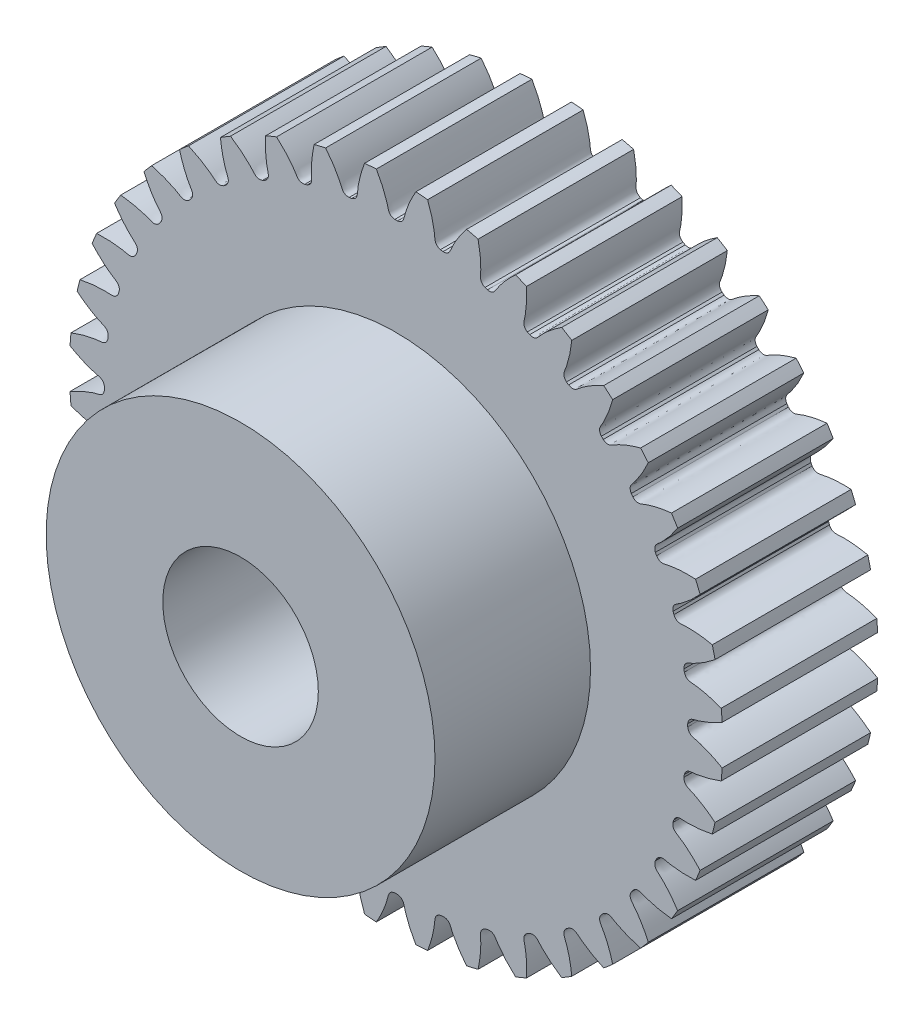
SolidWorks part; units mm, degrees
material "合金钢 (SS)"
ref_plane "前视基准面" through (0, 0, 0) normal (0, 0, 1) x (1, 0, 0)
ref_plane "上视基准面" through (0, 0, 0) normal (0, 1, 0) x (1, 0, 0)
ref_plane "右视基准面" through (0, 0, 0) normal (1, 0, 0) x (0, 0, -1)
other "Configuration Table"
sketch "草图1" plane through (0, 0, 0) normal (0, 0, 1) x (1, 0, 0)
  circle A0 centre (0, 0) radius 21
extrude "凸台-拉伸1" add sketch "草图1" along normal blind 10
ref_axis "基准轴1" through (0, 0, -1.5) along (0, 0, 1)
sketch "草图2" plane through (0, 0, 0) normal (0, 0, 1) x (1, 0, 0)
  line L0 (0, 0) -> (0, 21) construction
  circle A0 centre (0, 0) radius 21 construction
  arc A1 (0.0846, 18.7498) -> (-0.0846, 18.7498) centre (0, 0) ccw
  arc A2 (3.6741, 23.878) -> (-3.6741, 23.878) centre (0, 0) ccw
  spline S0 degree 3 poles (0.0846, 18.7498) (0.4557, 18.804) (0.4895, 19.0705) (0.567, 19.3562) (0.5939, 19.4493) (0.625, 19.5489) (0.6605, 19.6551) (0.7006, 19.7676) (0.7456, 19.8863) (0.7958, 20.011) (0.8514, 20.1417) (0.9127, 20.2781) (0.9799, 20.42) (1.0533, 20.5672) (1.1331, 20.7197) (1.2196, 20.8771) (1.3129, 21.0392) (1.4134, 21.2059) (1.5211, 21.3769) (1.6364, 21.552) (1.7595, 21.731) (1.8904, 21.9136) (2.0295, 22.0995) (2.1769, 22.2885) (2.3328, 22.4804) (2.4974, 22.6749) (2.6708, 22.8717) (2.8532, 23.0705) (3.0447, 23.2711) (3.3159, 23.5441) (3.5282, 23.7451) (3.6741, 23.878) knots 0 0 0 0 0.110657 0.124739 0.140005 0.156457 0.174093 0.192913 0.212918 0.234108 0.256483 0.280042 0.304786 0.330714 0.357827 0.386125 0.415607 0.446274 0.478126 0.511162 0.545383 0.580789 0.617379 0.655154 0.694113 0.734257 0.775586 0.8181 0.861798 0.906681 1 1 1 1
  spline S1 degree 3 poles (-0.0846, 18.7498) (-0.4557, 18.804) (-0.4895, 19.0705) (-0.567, 19.3562) (-0.5939, 19.4493) (-0.625, 19.5489) (-0.6605, 19.6551) (-0.7006, 19.7676) (-0.7456, 19.8863) (-0.7958, 20.011) (-0.8514, 20.1417) (-0.9127, 20.2781) (-0.9799, 20.42) (-1.0533, 20.5672) (-1.1331, 20.7197) (-1.2196, 20.8771) (-1.3129, 21.0392) (-1.4134, 21.2059) (-1.5211, 21.3769) (-1.6364, 21.552) (-1.7595, 21.731) (-1.8904, 21.9136) (-2.0295, 22.0995) (-2.1769, 22.2885) (-2.3328, 22.4804) (-2.4974, 22.6749) (-2.6708, 22.8717) (-2.8532, 23.0705) (-3.0447, 23.2711) (-3.3159, 23.5441) (-3.5282, 23.7451) (-3.6741, 23.878) knots 0 0 0 0 0.110657 0.124739 0.140005 0.156457 0.174093 0.192913 0.212918 0.234108 0.256483 0.280042 0.304786 0.330714 0.357827 0.386125 0.415607 0.446274 0.478126 0.511162 0.545383 0.580789 0.617379 0.655154 0.694113 0.734257 0.775586 0.8181 0.861798 0.906681 1 1 1 1
extrude "切除-拉伸1" cut sketch "草图2" along normal through all
pattern_circular "阵列(圆周)1" count 40 every 9 about axis through (0, 0, -1.5) along (0, 0, 1) of "切除-拉伸1"
sketch "草图3" plane through (0, 0, 0) normal (0, 0, 1) x (1, 0, 0)
  circle A0 centre (0, 0) radius 20 construction
  dimension "Dn" = 40
sketch "草图4" plane through (0, 0, 10) normal (0, 0, 1) x (1, 0, 0)
  circle A0 centre (0, 0) radius 12.5
  dimension "D1" = 25
extrude "凸台-拉伸2" add sketch "草图4" along normal blind 10
sketch "草图5" plane through (0, 0, 20) normal (0, 0, 1) x (1, 0, 0)
  circle A0 centre (0, 0) radius 5
  dimension "D1" = 10
extrude "切除-拉伸2" cut sketch "草图5" against normal blind 28
